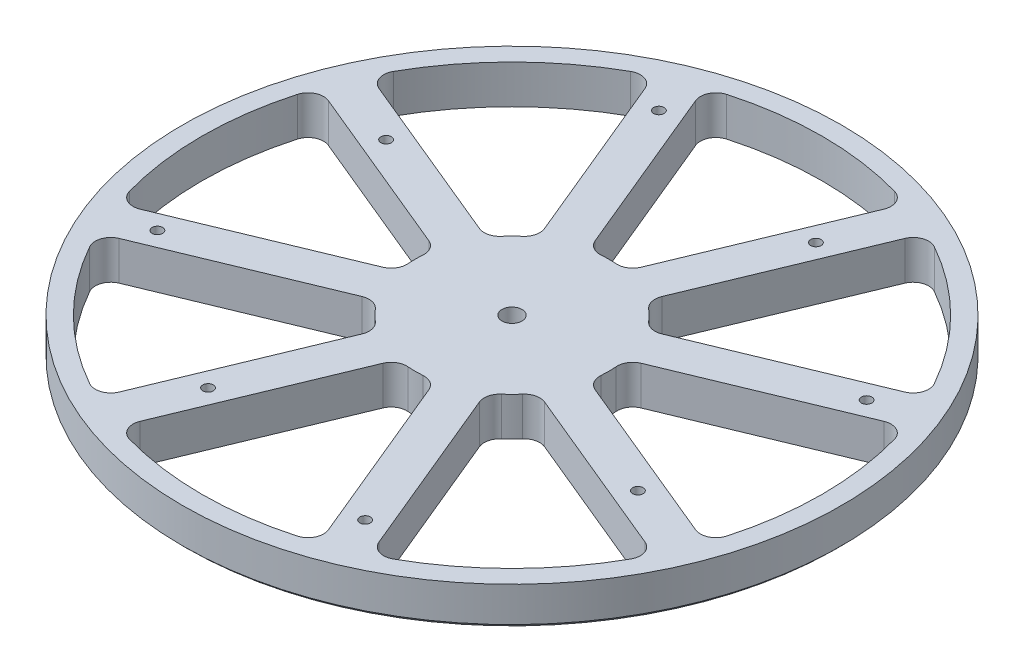
SolidWorks part; units mm, degrees
ref_plane "Front Plane" through (0, 0, 0) normal (0, 0, 1) x (1, 0, 0)
ref_plane "Top Plane" through (0, 0, 0) normal (0, 1, 0) x (1, 0, 0)
ref_plane "Right Plane" through (0, 0, 0) normal (1, 0, 0) x (0, 0, -1)
sketch "Sketch2" plane through (0, 0, 0) normal (1, 0, 0) x (0, 0, -1)
  line L0 (0, 0) -> (-84.9998, 0)
  line L1 (-84.9998, 0) -> (-84.9998, 10)
  line L2 (-84.9998, 10) -> (0, 10)
  line L5 (0, 10) -> (0, 0)
  dimension "D1" = 84.9998
  dimension "D2" = 10
ref_axis "Axis1" through (0, -0.5, 0) along (0, 1, 0)
revolve "Revolve1" add sketch "Sketch2" angle 360 about axis through (0, -0.5, 0) along (0, 1, 0)
hole_wizard "#6-32 Tapped Hole1" positions "Sketch6" profile "Sketch7" tap size "#6-32" standard "ANSI Inch" end condition through all
sketch "Sketch6" plane through (0, 10, 0) normal (0, 1, 0) x (1, 0, 0)
  line L0 (0, 0) -> (-53.438, 129.0108) construction
  line L2 (0, 0) -> (0, 109.0908) construction
  line L3 (0, 0) -> (-78.5296, 32.528) construction
  circle A0 centre (0, 0) radius 84.9998 construction
  point P0 (-26.7878, 64.6716)
  point P18 (-55.4328, 22.961)
  dimension "D1" = 22.5
  dimension "D2" = 70
  dimension "D3" = 45
  dimension "D4" = 60
sketch "Sketch7" plane through (-26.7878, 10, -64.6716) normal (1, 0, 0) x (0, 0, 1)
  line L0 (0, 0) -> (0, 10)
  line L1 (0, 10) -> (1.3525, 10)
  line L2 (1.3525, 10) -> (1.3525, 0)
  line L5 (1.3525, 0) -> (0, 0)
  line L11 (0, -6.35) -> (0, 107.95) construction
  dimension "Thread Major Dia." = 2.7051
  dimension "Thru Tap Drill Depth" = 10
pattern_circular "CirPattern3" count 4 over 360 about axis through (0, -0.5, 0) along (0, 1, 0) of "#6-32 Tapped Hole1"
sketch "Sketch8" plane through (0, 10, 0) normal (0, 1, 0) x (1, 0, 0)
  line L4 (0, 0) -> (0, 93.9995) construction
  line L5 (0, 0) -> (113.8372, 0) construction
  line L6 (-4.7544, 24.5438) -> (-25.9354, 75.6791)
  line L7 (4.7544, 24.5438) -> (25.9354, 75.6791)
  line L8 (0, 0) -> (-26.7878, 64.6716) construction
  arc A0 (-4.7544, 24.5438) -> (4.7544, 24.5438) centre (0, 0) cw
  arc A1 (-25.9354, 75.6791) -> (25.9354, 75.6791) centre (0, 0) cw
  circle A2 centre (0, 0) radius 84.9998 construction
  dimension "D1" = 25
  dimension "D2" = 5
  dimension "D3" = 5
extrude "Cut-Extrude1" cut sketch "Sketch8" against normal through all
fillet "Fillet1" radius 4 4 edges at (4.7544, 5, -24.5438) (25.9354, 5, -75.6791) (-4.7544, 5, -24.5438) (-25.9354, 5, -75.6791)
pattern_circular "CirPattern4" count 8 over 360 about axis through (0, -0.5, 0) along (0, 1, 0) of "Cut-Extrude1", "Fillet1"
chamfer "Chamfer2" distance 1 angle 45 1 edges at (0, 0, -84.9998)
hole_wizard "#6 (0.204) Diameter Hole2" positions "Sketch9" profile "Sketch11" hole size "#6" standard "ANSI Inch" end condition through all
sketch "Sketch9" plane through (0, 0, 0) normal (0, -1, 0) x (-1, 0, 0)
  point P0 (0, 0)
sketch "Sketch11" plane through (0, 0, 0) normal (1, 0, 0) x (0, 0, -1)
  line L0 (0, 0) -> (0, 10)
  line L1 (0, 10) -> (2.5908, 10)
  line L2 (2.5908, 10) -> (2.5908, 0)
  line L5 (2.5908, 0) -> (0, 0)
  line L11 (0, -6.35) -> (0, 107.95) construction
  dimension "Thru Hole Dia." = 5.1816
  dimension "Thru Hole Depth" = 10
equation "\"TubeDiameter\" = 6.6929in"
equation "\"D1@Sketch2\"=\"TubeDiameter\"/2"
